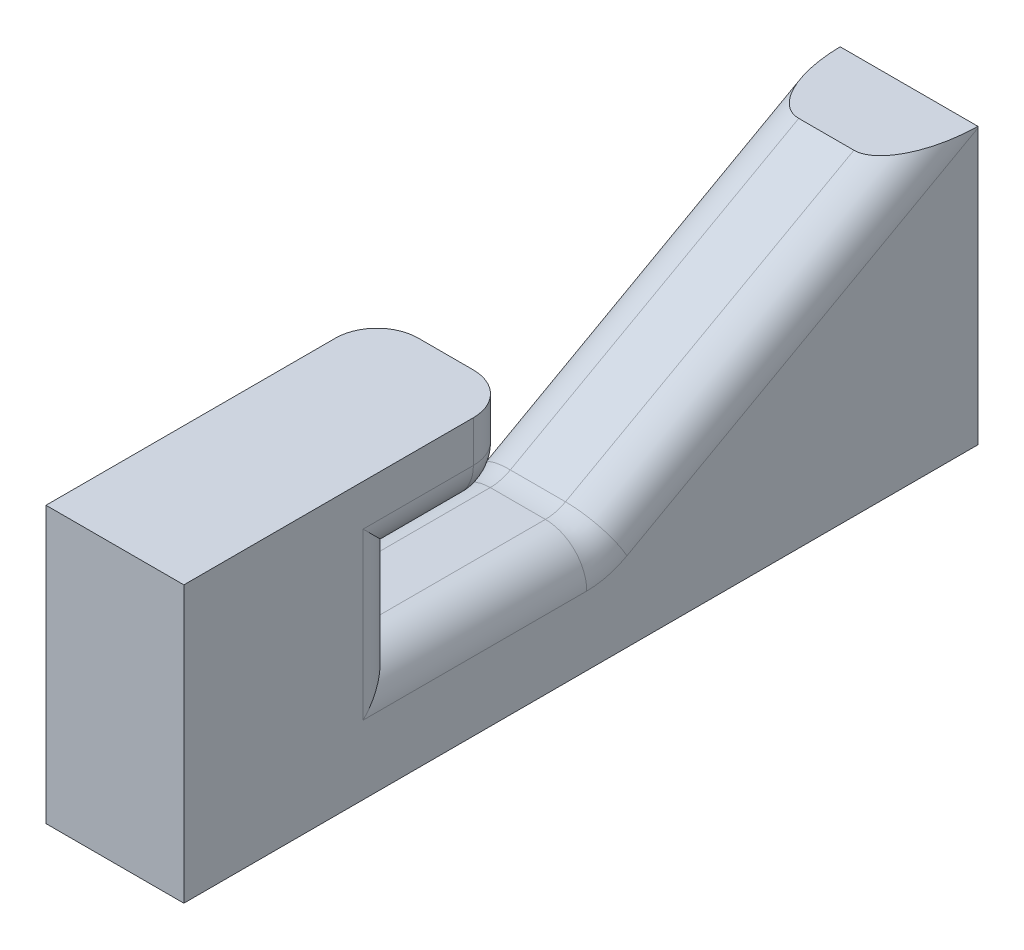
SolidWorks part; units mm, degrees
ref_plane "Front Plane" through (0, 0, 0) normal (1, 0, 0) x (0, 1, 0)
ref_plane "Top Plane" through (0, 0, 0) normal (0, 0, 1) x (0, 1, 0)
ref_plane "Right Plane" through (0, 0, 0) normal (0, 1, 0) x (-1, 0, 0)
sketch "Sketch2" plane through (0, 0, 0) normal (1, 0, 0) x (0, 1, 0)
  line L1 (0, 0) -> (10, 0)
  line L2 (0, 0) -> (0, 28.8)
  line L3 (0, 28.8) -> (10, 28.8)
  line L4 (10, 0) -> (10, 28.8)
  dimension "D1" = 28.8
  dimension "D2" = 10
extrude "Boss-Extrude1" add sketch "Sketch2" along normal blind 5
sketch "Sketch3" plane through (5, 0, 0) normal (1, 0, 0) x (0, 1, 0)
  line L0 (4, 16.8) -> (4, 13.8)
  line L1 (10, 28.8) -> (7, 28.8)
  line L2 (10, 28.8) -> (10, 16.8)
  line L3 (10, 16.8) -> (7, 16.8)
  line L4 (7, 28.8) -> (7, 16.8)
  line L5 (7, 16.8) -> (4, 16.8)
  line L6 (7, 16.8) -> (7, 20.8)
  line L7 (7, 20.8) -> (4, 20.8)
  line L8 (4, 16.8) -> (4, 20.8)
  line L10 (4, 13.8) -> (10, 3)
  line L11 (10, 0) -> (10, 28.8) construction
  line L12 (0, 0) -> (10, 0) construction
  line L13 (10, 3) -> (10, 16.8)
  line M12 (10, 0) -> (10, 28.8)
  dimension "D1" = 12
  dimension "D2" = 3
  dimension "D3" = 3
  dimension "D4" = 4
  dimension "D5" = 3
  dimension "D6" = 3
extrude "Cut-Extrude1" cut sketch "Sketch3" against normal through all contours L8 L5 L4 L7 | L0 L10 L3 L5 M12 region at (5, 7.6429, 12.0214) region at (5, 5.5, 18.8)
fillet "Fillet2" radius 1.5 12 edges at (2.5, 7, 16.8) (5, 7, 18.8) (5, 4, 17.3) (5, 5.5, 20.8) (0, 4, 17.3) (0, 5.5, 20.8) (0, 7, 18.8) (0, 7, 8.4) (5, 7, 8.4) (2.5, 4, 13.8) (0, 8.5, 16.8) (5, 8.5, 16.8)
equation "\"whitekey_cutout_length\"= 101.5"
equation "\"wall_thickness\"=10"
equation "\"base_mount_height\"=40"
equation "\"base_rear_length\"=80"
equation "\"D1@Sketch2\"=\"base_mount_height\"-11-0.2"
equation "\"key_mount_recess_length\"=50"
equation "\"key_mount_recess_height\"=12.5"
equation "\"key_mount_recess_depth\"=1.5"
equation "\"guide_brace_height\"=20"
equation "\"guide_brace_thickness\"=2"
equation "\"dowel_recess_depth\"=9"
equation "\"dowel_recess_offset\"=3.25"
equation "\"base_front_length\"=111.5"
equation "\"screw_hole_wall_offset\"=7.25"
equation "\"screw_hole_edge_inset\"=4.5"
equation "\"screw_hole_diameter\"=3.8"
equation "\"screw_head_hole_diameter\"=6.7"
equation "\"screw_nut_hole_side_len\"=3.5"
equation "\"screw_shaft_diameter\"=3.5"
equation "\"switch_board_width\"=30"
equation "\"heatset_insert_hole_diameter\"=4.8"
equation "\"heatset_insert_hole_depth\"=3.8"
